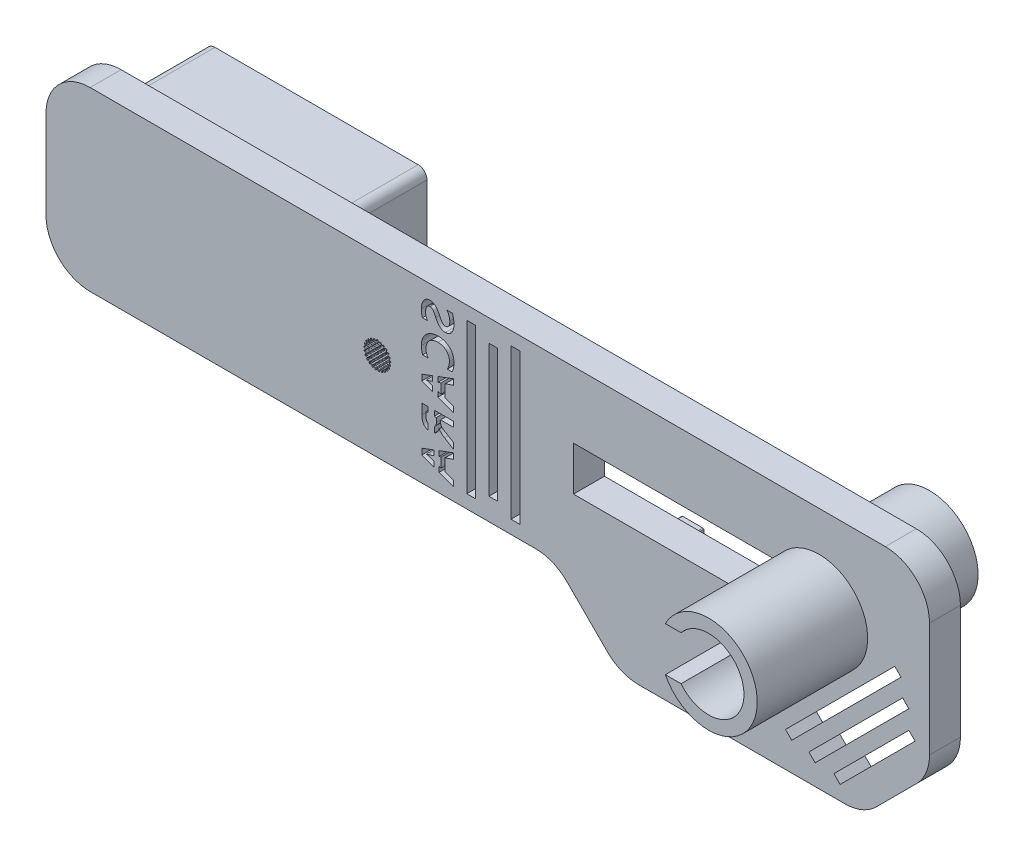
SolidWorks part; units mm, degrees
ref_plane "Alzado" through (0, 0, 0) normal (0, 0, 1) x (1, 0, 0)
ref_plane "Planta" through (0, 0, 0) normal (0, 1, 0) x (1, 0, 0)
ref_plane "Vista lateral" through (0, 0, 0) normal (1, 0, 0) x (0, 0, -1)
sketch "Croquis1" plane through (0, 0, 0) normal (0, 0, 1) x (1, 0, 0)
  line L0 (-64.25, 0) -> (10.75, 0) construction
  line L1 (0, 0) -> (0, -15.2525) construction
  line L2 (135.75, 20) -> (-64.25, 20)
  line L3 (135.75, 20) -> (135.75, -20)
  line L4 (135.75, -20) -> (-64.25, -20)
  line L5 (-64.25, 20) -> (-64.25, -20)
  line L56 (12.6265, 2.2468) -> (12.5286, 2.1823)
  line L57 (12.2759, 2.3659) -> (12.3069, 2.4789)
  line L58 (12.0088, 2.6428) -> (11.93, 2.5561)
  line L59 (11.6396, 2.6711) -> (11.6416, 2.7882)
  line L60 (11.312, 2.8728) -> (11.2572, 2.7692)
  line L61 (10.9474, 2.8084) -> (10.9201, 2.9223)
  line L62 (10.5799, 2.9223) -> (10.5526, 2.8084)
  line L63 (10.2428, 2.7692) -> (10.188, 2.8728)
  line L64 (9.8584, 2.7882) -> (9.8604, 2.6711)
  line L65 (9.57, 2.5561) -> (9.4912, 2.6428)
  line L66 (9.1931, 2.4789) -> (9.2241, 2.3659)
  line L67 (8.9714, 2.1823) -> (8.8735, 2.2468)
  line L68 (8.6255, 2.0138) -> (8.6836, 1.9121)
  line L69 (8.4846, 1.6715) -> (8.3738, 1.7095)
  line L70 (8.1914, 1.4222) -> (8.273, 1.3381)
  line L71 (8.1401, 1.0556) -> (8.0233, 1.0649)
  line L72 (7.9181, 0.7412) -> (8.0181, 0.6801)
  line L73 (7.9596, 0.3733) -> (7.8441, 0.3533)
  line L74 (7.8227, 0.0137) -> (7.9348, -0.0207)
  line L75 (7.9544, -0.3323) -> (7.8475, -0.3805)
  line L76 (7.9113, -0.7147) -> (8.0284, -0.7201)
  line L77 (8.1249, -1.0171) -> (8.0333, -1.0903)
  line L78 (8.1782, -1.3982) -> (8.293, -1.3744)
  line L79 (8.4603, -1.638) -> (8.3898, -1.7317)
  line L80 (8.6068, -1.9939) -> (8.7119, -1.9422)
  line L81 (8.9396, -2.156) -> (8.8946, -2.2642)
  line L82 (9.1699, -2.4642) -> (9.259, -2.3881)
  line L83 (9.5326, -2.5385) -> (9.516, -2.6545)
  line L84 (9.8324, -2.7798) -> (9.8997, -2.6838)
  line L85 (10.2022, -2.7615) -> (10.2149, -2.878)
  line L86 (10.5525, -2.9206) -> (10.5939, -2.811)
  line L87 (10.9061, -2.811) -> (10.9475, -2.9206)
  line L88 (11.2851, -2.878) -> (11.2978, -2.7615)
  line L89 (11.6003, -2.6838) -> (11.6676, -2.7798)
  line L90 (11.984, -2.6545) -> (11.9674, -2.5385)
  line L91 (12.241, -2.3881) -> (12.3301, -2.4642)
  line L92 (12.6054, -2.2642) -> (12.5604, -2.156)
  line L93 (12.7881, -1.9422) -> (12.8932, -1.9939)
  line L94 (13.1102, -1.7317) -> (13.0397, -1.638)
  line L95 (13.207, -1.3744) -> (13.3218, -1.3982)
  line L96 (13.4667, -1.0903) -> (13.3751, -1.0171)
  line L97 (13.4716, -0.7201) -> (13.5887, -0.7147)
  line L98 (13.6525, -0.3805) -> (13.5456, -0.3323)
  line L99 (13.5652, -0.0207) -> (13.6773, 0.0137)
  line L100 (13.6559, 0.3533) -> (13.5404, 0.3733)
  line L101 (13.4819, 0.6801) -> (13.5819, 0.7412)
  line L102 (13.4767, 1.0649) -> (13.3599, 1.0556)
  line L103 (13.227, 1.3381) -> (13.3086, 1.4222)
  line L104 (13.1262, 1.7095) -> (13.0154, 1.6715)
  line L105 (12.8164, 1.9121) -> (12.8745, 2.0138)
  line L106 (12.6265, 2.2468) -> (12.5286, 2.1823)
  line L107 (12.2759, 2.3659) -> (12.3069, 2.4789)
  line L108 (12.0088, 2.6428) -> (11.93, 2.5561)
  line L109 (11.6396, 2.6711) -> (11.6416, 2.7882)
  line L110 (11.312, 2.8728) -> (11.2572, 2.7692)
  line L111 (10.9474, 2.8084) -> (10.9201, 2.9223)
  line L112 (10.5799, 2.9223) -> (10.5526, 2.8084)
  line L113 (10.2428, 2.7692) -> (10.188, 2.8728)
  line L114 (9.8584, 2.7882) -> (9.8604, 2.6711)
  line L115 (9.57, 2.5561) -> (9.4912, 2.6428)
  line L116 (9.1931, 2.4789) -> (9.2241, 2.3659)
  line L117 (8.9714, 2.1823) -> (8.8735, 2.2468)
  line L118 (8.6255, 2.0138) -> (8.6836, 1.9121)
  line L119 (8.4846, 1.6715) -> (8.3738, 1.7095)
  line L120 (8.1914, 1.4222) -> (8.273, 1.3381)
  line L121 (8.1401, 1.0556) -> (8.0233, 1.0649)
  line L122 (7.9181, 0.7412) -> (8.0181, 0.6801)
  line L123 (7.9596, 0.3733) -> (7.8441, 0.3533)
  line L124 (7.8227, 0.0137) -> (7.9348, -0.0207)
  line L125 (7.9544, -0.3323) -> (7.8475, -0.3805)
  line L126 (7.9113, -0.7147) -> (8.0284, -0.7201)
  line L127 (8.1249, -1.0171) -> (8.0333, -1.0903)
  line L128 (8.1782, -1.3982) -> (8.293, -1.3744)
  line L129 (8.4603, -1.638) -> (8.3898, -1.7317)
  line L130 (8.6068, -1.9939) -> (8.7119, -1.9422)
  line L131 (8.9396, -2.156) -> (8.8946, -2.2642)
  line L132 (9.1699, -2.4642) -> (9.259, -2.3881)
  line L133 (9.5326, -2.5385) -> (9.516, -2.6545)
  line L134 (9.8324, -2.7798) -> (9.8997, -2.6838)
  line L135 (10.2022, -2.7615) -> (10.2149, -2.878)
  line L136 (10.5525, -2.9206) -> (10.5939, -2.811)
  line L137 (10.9061, -2.811) -> (10.9475, -2.9206)
  line L138 (11.2851, -2.878) -> (11.2978, -2.7615)
  line L139 (11.6003, -2.6838) -> (11.6676, -2.7798)
  line L140 (11.984, -2.6545) -> (11.9674, -2.5385)
  line L141 (12.241, -2.3881) -> (12.3301, -2.4642)
  line L142 (12.6054, -2.2642) -> (12.5604, -2.156)
  line L143 (12.7881, -1.9422) -> (12.8932, -1.9939)
  line L144 (13.1102, -1.7317) -> (13.0397, -1.638)
  line L145 (13.207, -1.3744) -> (13.3218, -1.3982)
  line L146 (13.4667, -1.0903) -> (13.3751, -1.0171)
  line L147 (13.4716, -0.7201) -> (13.5887, -0.7147)
  line L148 (13.6525, -0.3805) -> (13.5456, -0.3323)
  line L149 (13.5652, -0.0207) -> (13.6773, 0.0137)
  line L150 (13.6559, 0.3533) -> (13.5404, 0.3733)
  line L151 (13.4819, 0.6801) -> (13.5819, 0.7412)
  line L152 (13.4767, 1.0649) -> (13.3599, 1.0556)
  line L153 (13.227, 1.3381) -> (13.3086, 1.4222)
  line L154 (13.1262, 1.7095) -> (13.0154, 1.6715)
  line L155 (12.8164, 1.9121) -> (12.8745, 2.0138)
  arc A53 (12.8931, 2.1702) -> (12.7813, 2.2751) centre (10.75, 0) ccw
  arc A54 (12.2759, 2.3659) -> (12.5286, 2.1823) centre (12.4487, 2.3381) ccw
  arc A55 (12.2861, 2.635) -> (12.1517, 2.7088) centre (10.75, 0) ccw
  arc A56 (11.6396, 2.6711) -> (11.93, 2.5561) centre (11.8139, 2.6871) ccw
  arc A57 (11.5825, 2.9342) -> (11.434, 2.9723) centre (10.75, 0) ccw
  arc A58 (10.9474, 2.8084) -> (11.2572, 2.7692) centre (11.1122, 2.8672) ccw
  arc A59 (10.8267, 3.049) -> (10.6733, 3.049) centre (10.75, 0) ccw
  arc A60 (10.2428, 2.7692) -> (10.5526, 2.8084) centre (10.3878, 2.8672) ccw
  arc A61 (10.066, 2.9723) -> (9.9175, 2.9342) centre (10.75, 0) ccw
  arc A62 (9.57, 2.5561) -> (9.8604, 2.6711) centre (9.6861, 2.6871) ccw
  arc A63 (9.3483, 2.7088) -> (9.2139, 2.635) centre (10.75, 0) ccw
  arc A64 (8.9714, 2.1823) -> (9.2241, 2.3659) centre (9.0513, 2.3381) ccw
  arc A65 (8.7187, 2.2751) -> (8.6069, 2.1702) centre (10.75, 0) ccw
  arc A66 (8.4846, 1.6715) -> (8.6836, 1.9121) centre (8.5232, 1.8422) ccw
  arc A67 (8.2167, 1.6985) -> (8.1345, 1.569) centre (10.75, 0) ccw
  arc A68 (8.1401, 1.0556) -> (8.273, 1.3381) centre (8.135, 1.2305) ccw
  arc A69 (7.8739, 1.0151) -> (7.8265, 0.8693) centre (10.75, 0) ccw
  arc A70 (7.9596, 0.3733) -> (8.0181, 0.6801) centre (7.9112, 0.5415) ccw
  arc A71 (7.7118, 0.268) -> (7.7022, 0.1149) centre (10.75, 0) ccw
  arc A72 (7.9544, -0.3323) -> (7.9348, -0.0207) centre (7.8657, -0.1815) ccw
  arc A73 (7.7406, -0.496) -> (7.7693, -0.6466) centre (10.75, 0) ccw
  arc A74 (8.1249, -1.0171) -> (8.0284, -0.7201) centre (8.0014, -0.8931) ccw
  arc A75 (7.9585, -1.2289) -> (8.0238, -1.3676) centre (10.75, 0) ccw
  arc A76 (8.4603, -1.638) -> (8.293, -1.3744) centre (8.3099, -1.5485) ccw
  arc A77 (8.3518, -1.8845) -> (8.4495, -2.0026) centre (10.75, 0) ccw
  arc A78 (8.9396, -2.156) -> (8.7119, -1.9422) centre (8.7717, -2.1067) ccw
  arc A79 (8.8958, -2.4217) -> (9.0198, -2.5118) centre (10.75, 0) ccw
  arc A80 (9.5326, -2.5385) -> (9.259, -2.3881) centre (9.3577, -2.5325) ccw
  arc A81 (9.5563, -2.8067) -> (9.6988, -2.8631) centre (10.75, 0) ccw
  arc A82 (10.2022, -2.7615) -> (9.8997, -2.6838) centre (10.0313, -2.7992) ccw
  arc A83 (10.2918, -3.0154) -> (10.4439, -3.0346) centre (10.75, 0) ccw
  arc A84 (10.9061, -2.811) -> (10.5939, -2.811) centre (10.75, -2.89) ccw
  arc A85 (11.0561, -3.0346) -> (11.2082, -3.0154) centre (10.75, 0) ccw
  arc A86 (11.6003, -2.6838) -> (11.2978, -2.7615) centre (11.4687, -2.7992) ccw
  arc A87 (11.8012, -2.8631) -> (11.9437, -2.8067) centre (10.75, 0) ccw
  arc A88 (12.241, -2.3881) -> (11.9674, -2.5385) centre (12.1423, -2.5325) ccw
  arc A89 (12.4802, -2.5118) -> (12.6042, -2.4217) centre (10.75, 0) ccw
  arc A90 (12.7881, -1.9422) -> (12.5604, -2.156) centre (12.7283, -2.1067) ccw
  arc A91 (13.0505, -2.0026) -> (13.1482, -1.8845) centre (10.75, 0) ccw
  arc A92 (13.207, -1.3744) -> (13.0397, -1.638) centre (13.1901, -1.5485) ccw
  arc A93 (13.4762, -1.3676) -> (13.5415, -1.2289) centre (10.75, 0) ccw
  arc A94 (13.4716, -0.7201) -> (13.3751, -1.0171) centre (13.4986, -0.8931) ccw
  arc A95 (13.7307, -0.6466) -> (13.7594, -0.496) centre (10.75, 0) ccw
  arc A96 (13.5652, -0.0207) -> (13.5456, -0.3323) centre (13.6343, -0.1815) ccw
  arc A97 (13.7978, 0.1149) -> (13.7882, 0.268) centre (10.75, 0) ccw
  arc A98 (13.4819, 0.6801) -> (13.5404, 0.3733) centre (13.5888, 0.5415) ccw
  arc A99 (13.6735, 0.8693) -> (13.6261, 1.0151) centre (10.75, 0) ccw
  arc A100 (13.227, 1.3381) -> (13.3599, 1.0556) centre (13.365, 1.2305) ccw
  arc A101 (13.3655, 1.569) -> (13.2833, 1.6985) centre (10.75, 0) ccw
  arc A102 (12.8164, 1.9121) -> (13.0154, 1.6715) centre (12.9768, 1.8422) ccw
  arc A103 (12.8931, 2.1702) -> (12.7813, 2.2751) centre (10.75, 0) ccw
  arc A104 (12.2759, 2.3659) -> (12.5286, 2.1823) centre (12.4487, 2.3381) ccw
  arc A105 (12.2861, 2.635) -> (12.1517, 2.7088) centre (10.75, 0) ccw
  arc A106 (11.6396, 2.6711) -> (11.93, 2.5561) centre (11.8139, 2.6871) ccw
  arc A107 (11.5825, 2.9342) -> (11.434, 2.9723) centre (10.75, 0) ccw
  arc A108 (10.9474, 2.8084) -> (11.2572, 2.7692) centre (11.1122, 2.8672) ccw
  arc A109 (10.8267, 3.049) -> (10.6733, 3.049) centre (10.75, 0) ccw
  arc A110 (10.2428, 2.7692) -> (10.5526, 2.8084) centre (10.3878, 2.8672) ccw
  arc A111 (10.066, 2.9723) -> (9.9175, 2.9342) centre (10.75, 0) ccw
  arc A112 (9.57, 2.5561) -> (9.8604, 2.6711) centre (9.6861, 2.6871) ccw
  arc A113 (9.3483, 2.7088) -> (9.2139, 2.635) centre (10.75, 0) ccw
  arc A114 (8.9714, 2.1823) -> (9.2241, 2.3659) centre (9.0513, 2.3381) ccw
  arc A115 (8.7187, 2.2751) -> (8.6069, 2.1702) centre (10.75, 0) ccw
  arc A116 (8.4846, 1.6715) -> (8.6836, 1.9121) centre (8.5232, 1.8422) ccw
  arc A117 (8.2167, 1.6985) -> (8.1345, 1.569) centre (10.75, 0) ccw
  arc A118 (8.1401, 1.0556) -> (8.273, 1.3381) centre (8.135, 1.2305) ccw
  arc A119 (7.8739, 1.0151) -> (7.8265, 0.8693) centre (10.75, 0) ccw
  arc A120 (7.9596, 0.3733) -> (8.0181, 0.6801) centre (7.9112, 0.5415) ccw
  arc A121 (7.7118, 0.268) -> (7.7022, 0.1149) centre (10.75, 0) ccw
  arc A122 (7.9544, -0.3323) -> (7.9348, -0.0207) centre (7.8657, -0.1815) ccw
  arc A123 (7.7406, -0.496) -> (7.7693, -0.6466) centre (10.75, 0) ccw
  arc A124 (8.1249, -1.0171) -> (8.0284, -0.7201) centre (8.0014, -0.8931) ccw
  arc A125 (7.9585, -1.2289) -> (8.0238, -1.3676) centre (10.75, 0) ccw
  arc A126 (8.4603, -1.638) -> (8.293, -1.3744) centre (8.3099, -1.5485) ccw
  arc A127 (8.3518, -1.8845) -> (8.4495, -2.0026) centre (10.75, 0) ccw
  arc A128 (8.9396, -2.156) -> (8.7119, -1.9422) centre (8.7717, -2.1067) ccw
  arc A129 (8.8958, -2.4217) -> (9.0198, -2.5118) centre (10.75, 0) ccw
  arc A130 (9.5326, -2.5385) -> (9.259, -2.3881) centre (9.3577, -2.5325) ccw
  arc A131 (9.5563, -2.8067) -> (9.6988, -2.8631) centre (10.75, 0) ccw
  arc A132 (10.2022, -2.7615) -> (9.8997, -2.6838) centre (10.0313, -2.7992) ccw
  arc A133 (10.2918, -3.0154) -> (10.4439, -3.0346) centre (10.75, 0) ccw
  arc A134 (10.9061, -2.811) -> (10.5939, -2.811) centre (10.75, -2.89) ccw
  arc A135 (11.0561, -3.0346) -> (11.2082, -3.0154) centre (10.75, 0) ccw
  arc A136 (11.6003, -2.6838) -> (11.2978, -2.7615) centre (11.4687, -2.7992) ccw
  arc A137 (11.8012, -2.8631) -> (11.9437, -2.8067) centre (10.75, 0) ccw
  arc A138 (12.241, -2.3881) -> (11.9674, -2.5385) centre (12.1423, -2.5325) ccw
  arc A139 (12.4802, -2.5118) -> (12.6042, -2.4217) centre (10.75, 0) ccw
  arc A140 (12.7881, -1.9422) -> (12.5604, -2.156) centre (12.7283, -2.1067) ccw
  arc A141 (13.0505, -2.0026) -> (13.1482, -1.8845) centre (10.75, 0) ccw
  arc A142 (13.207, -1.3744) -> (13.0397, -1.638) centre (13.1901, -1.5485) ccw
  arc A143 (13.4762, -1.3676) -> (13.5415, -1.2289) centre (10.75, 0) ccw
  arc A144 (13.4716, -0.7201) -> (13.3751, -1.0171) centre (13.4986, -0.8931) ccw
  arc A145 (13.7307, -0.6466) -> (13.7594, -0.496) centre (10.75, 0) ccw
  arc A146 (13.5652, -0.0207) -> (13.5456, -0.3323) centre (13.6343, -0.1815) ccw
  arc A147 (13.7978, 0.1149) -> (13.7882, 0.268) centre (10.75, 0) ccw
  arc A148 (13.4819, 0.6801) -> (13.5404, 0.3733) centre (13.5888, 0.5415) ccw
  arc A149 (13.6735, 0.8693) -> (13.6261, 1.0151) centre (10.75, 0) ccw
  arc A150 (13.227, 1.3381) -> (13.3599, 1.0556) centre (13.365, 1.2305) ccw
  arc A151 (13.3655, 1.569) -> (13.2833, 1.6985) centre (10.75, 0) ccw
  arc A152 (12.8164, 1.9121) -> (13.0154, 1.6715) centre (12.9768, 1.8422) ccw
  spline S50 degree 3 poles (4995.73, -409.2684) (-67.7848, 26.1915) (12.1151, -1.3356) (12.9076, 2.1011) (12.9095, 2.115) (12.8385, 3.3562) (-8.2992, 15.6916) (-3096.0511, -3912.7164) knots -64.209924 -64.209924 -64.209924 -64.209924 0.5 0.5 0.75 0.75 22.340725 22.340725 22.340725 22.340725 only from (12.8745, 2.0138) to (12.8931, 2.1702)
  spline S51 degree 3 poles (-3620.5843, -3431.6551) (26.5308, -18.348) (13.985, 2.2945) (12.7252, 2.2881) (12.7115, 2.2853) (9.3593, 1.2884) (40.0278, -76.1834) (-376.9025, 4986.8401) knots -21.531354 -21.531354 -21.531354 -21.531354 0.25 0.25 0.5 0.5 64.672739 64.672739 64.672739 64.672739 only from (12.7813, 2.2751) to (12.6265, 2.2468)
  spline S52 degree 3 poles (4940.8986, 843.3036) (-71.831, 5.8378) (12.4044, -0.9542) (12.3173, 2.5717) (12.3157, 2.5856) (11.9382, 3.7702) (-11.603, 10.4612) (-2025.3923, -4562.4212) knots -64.209924 -64.209924 -64.209924 -64.209924 0.5 0.5 0.75 0.75 22.340725 22.340725 22.340725 22.340725 only from (12.3069, 2.4789) to (12.2861, 2.635)
  spline S53 degree 3 poles (-2653.0813, -4226.9195) (30.598, -13.847) (13.3128, 3.027) (12.0941, 2.7074) (12.0816, 2.7013) (9.0826, 0.9021) (58.054, -66.5088) (-1604.9003, 4733.7641) knots -21.531354 -21.531354 -21.531354 -21.531354 0.25 0.25 0.5 0.5 64.672739 64.672739 64.672739 64.672739 only from (12.1517, 2.7088) to (12.0088, 2.6428)
  spline S54 degree 3 poles (4576.2878, 2042.8878) (-70.6884, -14.8827) (12.5897, -0.5128) (11.6285, 2.8806) (11.6235, 2.8938) (10.9633, 3.9472) (-13.5024, 4.5736) (-826.7951, -4925.4523) knots -64.209924 -64.209924 -64.209924 -64.209924 0.5 0.5 0.75 0.75 22.340725 22.340725 22.340725 22.340725 only from (11.6416, 2.7882) to (11.5825, 2.9342)
  spline S55 degree 3 poles (-1518.2, -4756.5909) (33.418, -8.476) (12.4795, 3.5692) (11.3786, 2.9566) (11.368, 2.9476) (8.9107, 0.4591) (73.1079, -52.6553) (-2731.381, 4183.2483) knots -21.531354 -21.531354 -21.531354 -21.531354 0.25 0.25 0.5 0.5 64.672739 64.672739 64.672739 64.672739 only from (11.434, 2.9723) to (11.312, 2.8728)
  spline S56 degree 3 poles (3924.8075, 3114.1098) (-64.4287, -34.668) (12.6594, -0.0391) (10.8845, 3.0086) (10.8764, 3.0201) (9.9749, 3.8762) (-13.8779, -1.6014) (424.4281, -4978.9992) knots -64.209924 -64.209924 -64.209924 -64.209924 0.5 0.5 0.75 0.75 22.340725 22.340725 22.340725 22.340725 only from (10.9201, 2.9223) to (10.8267, 3.049)
  spline S57 degree 3 poles (-287.2492, -4987.3883) (34.8138, -2.5724) (11.5375, 3.8872) (10.6236, 3.0201) (10.6155, 3.0087) (8.8543, -0.0128) (84.2437, -35.4933) (-3685.5634, 3369.8836) knots -21.531354 -21.531354 -21.531354 -21.531354 0.25 0.25 0.5 0.5 64.672739 64.672739 64.672739 64.672739 only from (10.6733, 3.049) to (10.5799, 2.9223)
  spline S58 degree 3 poles (3027.3926, 3989.6608) (-53.4452, -52.275) (12.6092, 0.437) (10.1321, 2.9476) (10.1214, 2.9566) (9.0353, 3.5617) (-12.7059, -7.6758) (1649.6584, -4719.6972) knots -64.209924 -64.209924 -64.209924 -64.209924 0.5 0.5 0.75 0.75 22.340725 22.340725 22.340725 22.340725 only from (10.188, 2.8728) to (10.066, 2.9723)
  spline S59 degree 3 poles (962.4261, -4904.8097) (34.6975, 3.4928) (10.5461, 3.9609) (9.8765, 2.8938) (9.8715, 2.8807) (8.917, -0.4838) (90.7616, -16.101) (-4407.4929, 2344.7767) knots -21.531354 -21.531354 -21.531354 -21.531354 0.25 0.25 0.5 0.5 64.672739 64.672739 64.672739 64.672739 only from (9.9175, 2.9342) to (9.8584, 2.7882)
  spline S60 degree 3 poles (1940.4309, 4614.5268) (-38.4281, -66.5974) (12.4421, 0.8856) (9.4185, 2.7013) (9.4058, 2.7074) (8.2034, 3.0234) (-10.0601, -13.2679) (2771.91, -4163.8393) knots -64.209924 -64.209924 -64.209924 -64.209924 0.5 0.5 0.75 0.75 22.340725 22.340725 22.340725 22.340725 only from (9.4912, 2.6428) to (9.3483, 2.7088)
  spline S61 degree 3 poles (2152.304, -4514.0439) (33.0765, 9.3386) (9.5675, 3.7857) (9.1843, 2.5856) (9.1827, 2.5717) (9.0949, -0.9245) (92.252, 4.3029) (-4851.8079, 1172.3389) knots -21.531354 -21.531354 -21.531354 -21.531354 0.25 0.25 0.5 0.5 64.672739 64.672739 64.672739 64.672739 only from (9.2139, 2.635) to (9.1931, 2.4789)
  spline S62 degree 3 poles (732.2203, 4949.4451) (-20.321, -76.7352) (12.1687, 1.2786) (8.7885, 2.2853) (8.7748, 2.2881) (7.5315, 2.2951) (-6.1067, -18.0263) (3720.6678, -3346.3521) knots -64.209924 -64.209924 -64.209924 -64.209924 0.5 0.5 0.75 0.75 22.340725 22.340725 22.340725 22.340725 only from (8.8735, 2.2468) to (8.7187, 2.2751)
  spline S63 degree 3 poles (3207.6202, -3839.6441) (30.0527, 14.5976) (8.6631, 3.3727) (8.5904, 2.115) (8.5924, 2.1012) (9.3768, -1.307) (88.6214, 24.4364) (-4990.5906, -73.7612) knots -21.531354 -21.531354 -21.531354 -21.531354 0.25 0.25 0.5 0.5 64.672739 64.672739 64.672739 64.672739 only from (8.6069, 2.1702) to (8.6255, 2.0138)
  spline S64 degree 3 poles (-521.323, 4973.3715) (-0.2616, -82.0515) (11.8062, 1.5912) (8.2818, 1.7257) (8.2678, 1.725) (7.0619, 1.4226) (-1.0942, -21.6521) (4436.3179, -2318.6012) knots -64.209924 -64.209924 -64.209924 -64.209924 0.5 0.5 0.75 0.75 22.340725 22.340725 22.340725 22.340725 only from (8.3738, 1.7095) to (8.2167, 1.6985)
  spline S65 degree 3 poles (4062.0653, -2923.9853) (25.816, 18.9393) (7.8899, 2.7478) (8.1323, 1.5115) (8.1376, 1.4986) (9.745, -1.6075) (80.0978, 43.0345) (-4815.1206, -1315.2267) knots -21.531354 -21.531354 -21.531354 -21.531354 0.25 0.25 0.5 0.5 64.672739 64.672739 64.672739 64.672739 only from (8.1345, 1.569) to (8.1914, 1.4222)
  spline S66 degree 3 poles (-1741.4341, 4684.8028) (20.4897, -82.2122) (11.3773, 1.8039) (7.9302, 1.0577) (7.9168, 1.0535) (6.824, 0.4607) (4.6626, -23.9173) (4873.8932, -1145.1641) knots -64.209924 -64.209924 -64.209924 -64.209924 0.5 0.5 0.75 0.75 22.340725 22.340725 22.340725 22.340725 only from (8.0233, 1.0649) to (7.8739, 1.0151)
  spline S67 degree 3 poles (4661.9513, -1824.6018) (20.6326, 22.0911) (7.2964, 1.9502) (7.8387, 0.813) (7.847, 0.8018) (10.1764, -1.8069) (67.2169, 58.9286) (-4336.4234, -2474.0517) knots -21.531354 -21.531354 -21.531354 -21.531354 0.25 0.25 0.5 0.5 64.672739 64.672739 64.672739 64.672739 only from (7.8265, 0.8693) to (7.9181, 0.7412)
  spline S68 degree 3 poles (-2851.4491, 4101.8706) (40.6291, -77.2071) (10.9089, 1.9032) (7.7558, 0.3232) (7.7438, 0.3158) (6.8327, -0.5301) (10.8018, -24.6798) (5005.8993, 100.2278) knots -64.209924 -64.209924 -64.209924 -64.209924 0.5 0.5 0.75 0.75 22.340725 22.340725 22.340725 22.340725 only from (7.8441, 0.3533) to (7.7118, 0.268)
  spline S69 degree 3 poles (4969.5853, -610.5718) (14.8283, 23.8547) (6.9199, 1.03) (7.7279, 0.0635) (7.7388, 0.0547) (10.6437, -1.8928) (50.7879, 71.12) (-3584.5773, -3477.4228) knots -21.531354 -21.531354 -21.531354 -21.531354 0.25 0.25 0.5 0.5 64.672739 64.672739 64.672739 64.672739 only from (7.7022, 0.1149) to (7.8227, 0.0137)
  spline S70 degree 3 poles (-3781.6216, 3261.2028) (58.891, -67.3509) (10.4306, 1.8829) (7.7695, -0.4316) (7.7597, -0.4417) (7.0877, -1.4877) (16.9378, -23.8916) (4824.0419, 1339.3221) knots -64.209924 -64.209924 -64.209924 -64.209924 0.5 0.5 0.75 0.75 22.340725 22.340725 22.340725 22.340725 only from (7.8475, -0.3805) to (7.7406, -0.496)
  spline S71 degree 3 poles (4965.6374, 641.8226) (8.7677, 24.1195) (6.7841, 0.0452) (7.8071, -0.6901) (7.8198, -0.6959) (11.1178, -1.8597) (31.8432, 78.8427) (-2606.8236, -4262.2948) knots -21.531354 -21.531354 -21.531354 -21.531354 0.25 0.25 0.5 0.5 64.672739 64.672739 64.672739 64.672739 only from (7.7693, -0.6466) to (7.9113, -0.7147)
  spline S72 degree 3 poles (-4473.5054, 2215.6217) (74.1281, -53.2628) (9.9724, 1.7444) (7.9704, -1.1593) (7.9635, -1.1715) (7.5727, -2.3517) (22.685, -21.6021) (4339.7476, 2494.2619) knots -64.209924 -64.209924 -64.209924 -64.209924 0.5 0.5 0.75 0.75 22.340725 22.340725 22.340725 22.340725 only from (8.0333, -1.0903) to (7.9585, -1.2289)
  spline S73 degree 3 poles (4650.3557, 1853.8889) (2.8317, 22.8688) (6.8975, -0.9425) (8.0712, -1.4003) (8.0849, -1.4027) (11.5687, -1.7098) (11.5732, 81.6114) (-1464.5981, -4779.351) knots -21.531354 -21.531354 -21.531354 -21.531354 0.25 0.25 0.5 0.5 64.672739 64.672739 64.672739 64.672739 only from (8.0238, -1.3676) to (8.1782, -1.3982)
  spline S74 degree 3 poles (-4883.627, 1030.8249) (85.3828, -35.828) (9.563, 1.4962) (8.3461, -1.8141) (8.3424, -1.8277) (8.2573, -3.068) (27.6823, -17.9553) (3583.4465, 3492.478) knots -64.209924 -64.209924 -64.209924 -64.209924 0.5 0.5 0.75 0.75 22.340725 22.340725 22.340725 22.340725 only from (8.3898, -1.7317) to (8.3518, -1.8845)
  spline S75 degree 3 poles (4043.5505, 2949.4686) (-2.6067, 20.1812) (7.2529, -1.871) (8.5036, -2.0225) (8.5175, -2.0214) (11.9682, -1.4525) (-8.7486, 79.2521) (-229.6711, -4996.1031) knots -21.531354 -21.531354 -21.531354 -21.531354 0.25 0.25 0.5 0.5 64.672739 64.672739 64.672739 64.672739 only from (8.4495, -2.0026) to (8.6068, -1.9939)
  spline S76 degree 3 poles (-4986.2169, -218.7425) (91.9482, -16.1419) (9.2282, 1.154) (8.8727, -2.3549) (8.8726, -2.369) (9.0986, -3.5915) (31.6156, -13.1803) (2602.6597, 4271.2488) knots -64.209924 -64.209924 -64.209924 -64.209924 0.5 0.5 0.75 0.75 22.340725 22.340725 22.340725 22.340725 only from (8.8946, -2.2642) to (8.8958, -2.4217)
  spline S77 degree 3 poles (3183.3497, 3859.7224) (-7.206, 16.2254) (7.8281, -2.6819) (9.0771, -2.5176) (9.0903, -2.5131) (12.2912, -1.1039) (-27.8452, 71.9132) (1020.3625, -4898.9316) knots -21.531354 -21.531354 -21.531354 -21.531354 0.25 0.25 0.5 0.5 64.672739 64.672739 64.672739 64.672739 only from (9.0198, -2.5118) to (9.1699, -2.4642)
  spline S78 degree 3 poles (-4774.8289, -1454.5654) (93.4115, 4.5584) (8.9891, 0.7393) (9.5174, -2.7478) (9.5207, -2.7615) (10.0437, -3.8894) (34.2379, -7.5772) (1459.0137, 4781.6414) knots -64.209924 -64.209924 -64.209924 -64.209924 0.5 0.5 0.75 0.75 22.340725 22.340725 22.340725 22.340725 only from (9.516, -2.6545) to (9.5563, -2.8067)
  spline S79 degree 3 poles (2123.8027, 4527.4555) (-10.6769, 11.2502) (8.5868, -3.3243) (9.7558, -2.8545) (9.7675, -2.8469) (12.5173, -0.686) (-44.5168, 60.0556) (2206.9584, -4493.9422) knots -21.531354 -21.531354 -21.531354 -21.531354 0.25 0.25 0.5 0.5 64.672739 64.672739 64.672739 64.672739 only from (9.6988, -2.8631) to (9.8324, -2.7798)
  spline S80 degree 3 poles (-4262.7455, -2598.9926) (89.6809, 24.9722) (8.8605, 0.2781) (10.2394, -2.968) (10.2461, -2.9804) (11.0331, -3.9428) (35.3844, -1.4979) (224.368, 4991.5859) knots -64.209924 -64.209924 -64.209924 -64.209924 0.5 0.5 0.75 0.75 22.340725 22.340725 22.340725 22.340725 only from (10.2149, -2.878) to (10.2918, -3.0154)
  spline S81 degree 3 poles (931.4849, 4910.712) (-12.8016, 5.5681) (9.4815, -3.7578) (10.4969, -3.0121) (10.5063, -3.0018) (12.6324, -0.2249) (-57.7157, 44.4246) (3255.5585, -3806.5819) knots -21.531354 -21.531354 -21.531354 -21.531354 0.25 0.25 0.5 0.5 64.672739 64.672739 64.672739 64.672739 only from (10.4439, -3.0346) to (10.5525, -2.9206)
  spline S82 degree 3 poles (-3482.1426, -3580.1156) (80.9908, 43.817) (8.8507, -0.2005) (10.9936, -3.0018) (11.0031, -3.0121) (12.0048, -3.7485) (34.983, 4.6755) (-1023.7002, 4887.8907) knots -64.209924 -64.209924 -64.209924 -64.209924 0.5 0.5 0.75 0.75 22.340725 22.340725 22.340725 22.340725 only from (10.9475, -2.9206) to (11.0561, -3.0346)
  spline S83 degree 3 poles (-318.6861, 4985.4104) (-13.4464, -0.4639) (10.4559, -3.9552) (11.2539, -2.9804) (11.2605, -2.9681) (12.6292, 0.2503) (-66.6127, 26.0022) (4100.2753, -2880.0401) knots -21.531354 -21.531354 -21.531354 -21.531354 0.25 0.25 0.5 0.5 64.672739 64.672739 64.672739 64.672739 only from (11.2082, -3.0154) to (11.2851, -2.878)
  spline S84 degree 3 poles (-2482.0684, -4336.2867) (67.8872, 59.9086) (8.9603, -0.6665) (11.7325, -2.8469) (11.7442, -2.8545) (12.8976, -3.3187) (33.0589, 10.5551) (-2206.77, 4477.0713) knots -64.209924 -64.209924 -64.209924 -64.209924 0.5 0.5 0.75 0.75 22.340725 22.340725 22.340725 22.340725 only from (11.6676, -2.7798) to (11.8012, -2.8631)
  spline S85 degree 3 poles (-1548.1575, 4746.8572) (-12.5709, -6.4667) (11.4487, -3.9041) (11.9793, -2.7615) (11.9826, -2.7479) (12.5079, 0.7097) (-70.6487, 5.946) (4688.0322, -1772.5348) knots -21.531354 -21.531354 -21.531354 -21.531354 0.25 0.25 0.5 0.5 64.672739 64.672739 64.672739 64.672739 only from (11.9437, -2.8067) to (11.984, -2.6545)
  spline S86 degree 3 poles (-1325.3612, -4819.993) (51.1935, 72.2359) (9.1822, -1.0907) (12.4096, -2.5131) (12.4229, -2.5176) (13.6554, -2.6804) (29.7331, 15.7715) (-3250.5049, 3784.9411) knots -64.209924 -64.209924 -64.209924 -64.209924 0.5 0.5 0.75 0.75 22.340725 22.340725 22.340725 22.340725 only from (12.3301, -2.4642) to (12.4802, -2.5118)
  spline S87 degree 3 poles (-2679.6769, 4210.0414) (-10.23, -12.0632) (12.3977, -3.6077) (12.6274, -2.369) (12.6273, -2.355) (12.2761, 1.1246) (-69.5701, -14.4839) (4981.8982, -553.6546) knots -21.531354 -21.531354 -21.531354 -21.531354 0.25 0.25 0.5 0.5 64.672739 64.672739 64.672739 64.672739 only from (12.6042, -2.4217) to (12.6054, -2.2642)
  spline S88 degree 3 poles (-84.7013, -5000.8414) (31.9585, 80.0244) (9.5027, -1.4463) (12.9824, -2.0214) (12.9964, -2.0225) (14.2307, -1.8736) (25.2145, 19.9969) (-4089.3232, 2854.9891) knots -64.209924 -64.209924 -64.209924 -64.209924 0.5 0.5 0.75 0.75 22.340725 22.340725 22.340725 22.340725 only from (12.8932, -1.9939) to (13.0505, -2.0026)
  spline S89 degree 3 poles (-3642.1469, 3408.6932) (-6.5709, -16.9017) (13.2431, -3.0846) (13.1576, -1.8277) (13.154, -1.8142) (11.9485, 1.4688) (-63.4447, -34.0036) (4963.4088, 700.0138) knots -21.531354 -21.531354 -21.531354 -21.531354 0.25 0.25 0.5 0.5 64.672739 64.672739 64.672739 64.672739 only from (13.1482, -1.8845) to (13.1102, -1.7317)
  spline S90 degree 3 poles (1161.9561, -4867.4686) (11.391, 82.7846) (9.9016, -1.711) (13.415, -1.4027) (13.4288, -1.4003) (14.5873, -0.9491) (19.787, 22.9658) (-4670.5187, 1745.6476) knots -64.209924 -64.209924 -64.209924 -64.209924 0.5 0.5 0.75 0.75 22.340725 22.340725 22.340725 22.340725 only from (13.3218, -1.3982) to (13.4762, -1.3676)
  spline S91 degree 3 poles (-4375.092, 2393.1644) (-1.8234, -20.6783) (13.9319, -2.3677) (13.5365, -1.1715) (13.5296, -1.1593) (11.5456, 1.7207) (-52.6574, -51.3868) (4633.7255, 1909.6977) knots -21.531354 -21.531354 -21.531354 -21.531354 0.25 0.25 0.5 0.5 64.672739 64.672739 64.672739 64.672739 only from (13.5415, -1.2289) to (13.4667, -1.0903)
  spline S92 degree 3 poles (2336.2791, -4428.2548) (-9.2169, 80.3432) (10.3538, -1.8683) (13.6801, -0.6959) (13.6929, -0.6901) (14.7028, 0.035) (13.7918, 24.4917) (-4957.573, 526.6207) knots -64.209924 -64.209924 -64.209924 -64.209924 0.5 0.5 0.75 0.75 22.340725 22.340725 22.340725 22.340725 only from (13.5887, -0.7147) to (13.7307, -0.6466)
  spline S93 degree 3 poles (-4832.4585, 1227.2642) (3.7141, -23.1555) (14.4208, -1.502) (13.7403, -0.4417) (13.7306, -0.4317) (11.0927, 1.8645) (-37.8859, -65.5411) (4013.5637, 2999.3883) knots -21.531354 -21.531354 -21.531354 -21.531354 0.25 0.25 0.5 0.5 64.672739 64.672739 64.672739 64.672739 only from (13.7594, -0.496) to (13.6525, -0.3805)
  spline S94 degree 3 poles (3364.4805, -3710.7974) (-28.5701, 72.8535) (10.8308, -1.9081) (13.7611, 0.0546) (13.7721, 0.0635) (14.5699, 1.0169) (7.6054, 24.4787) (-4932.4492, -725.4957) knots -64.209924 -64.209924 -64.209924 -64.209924 0.5 0.5 0.75 0.75 22.340725 22.340725 22.340725 22.340725 only from (13.6773, 0.0137) to (13.7978, 0.1149)
  spline S95 degree 3 poles (-4985.5083, -15.7496) (9.6936, -24.1778) (14.679, -0.5419) (13.7562, 0.3158) (13.7443, 0.3231) (10.6182, 1.8912) (-20.0585, -75.5773) (3141.8904, 3900.6163) knots -21.531354 -21.531354 -21.531354 -21.531354 0.25 0.25 0.5 0.5 64.672739 64.672739 64.672739 64.672739 only from (13.7882, 0.268) to (13.6559, 0.3533)
  spline S96 degree 3 poles (4181.9547, -2760.1771) (-45.4527, 60.7862) (11.3028, -1.8281) (13.6529, 0.8018) (13.6613, 0.813) (14.197, 1.935) (1.6165, 22.9276) (-4596.7261, -1932.0266) knots -64.209924 -64.209924 -64.209924 -64.209924 0.5 0.5 0.75 0.75 22.340725 22.340725 22.340725 22.340725 only from (13.5819, 0.7412) to (13.6735, 0.8693)
  spline S97 degree 3 poles (-4824.6249, -1257.7737) (15.7396, -23.6809) (14.6903, 0.4522) (13.5832, 1.0535) (13.5699, 1.0577) (10.152, 1.799) (-0.2953, -80.8647) (2073.4761, 4556.7543) knots -21.531354 -21.531354 -21.531354 -21.531354 0.25 0.25 0.5 0.5 64.672739 64.672739 64.672739 64.672739 only from (13.6261, 1.0151) to (13.4767, 1.0649)
  spline S98 degree 3 poles (4737.3368, -1636.1246) (-58.8039, 44.8994) (11.7401, -1.6331) (13.3624, 1.4985) (13.3677, 1.5115) (13.6075, 2.7314) (-3.7984, 19.9359) (-3971.4983, -3017.1611) knots -64.209924 -64.209924 -64.209924 -64.209924 0.5 0.5 0.75 0.75 22.340725 22.340725 22.340725 22.340725 only from (13.3086, 1.4222) to (13.3655, 1.569)
  spline S99 degree 3 poles (-4359.9171, -2420.7673) (21.4721, -21.6961) (14.454, 1.4179) (13.2322, 1.725) (13.2183, 1.7257) (9.7234, 1.5937) (20.1619, -81.071) (875.453, 4926.5746) knots -21.531354 -21.531354 -21.531354 -21.531354 0.25 0.25 0.5 0.5 64.672739 64.672739 64.672739 64.672739 only from (13.2833, 1.6985) to (13.1262, 1.7095)
  spline S100 degree 3 poles (12.8745, 2.0138) (12.8876, 2.0368) (12.8985, 2.0614) (12.9076, 2.1011) (12.9095, 2.115) (12.9079, 2.1434) (12.9043, 2.1591) (12.8931, 2.1702) knots 0 0 0 0 0.5 0.5 0.75 0.75 1 1 1 1
  spline S101 degree 3 poles (12.7813, 2.2751) (12.7696, 2.2856) (12.7538, 2.2882) (12.7252, 2.2881) (12.7115, 2.2853) (12.6725, 2.2737) (12.6486, 2.2613) (12.6265, 2.2468) knots 0 0 0 0 0.25 0.25 0.5 0.5 1 1 1 1
  spline S102 degree 3 poles (12.3069, 2.4789) (12.314, 2.5044) (12.3183, 2.531) (12.3173, 2.5717) (12.3157, 2.5856) (12.3071, 2.6127) (12.2996, 2.627) (12.2861, 2.635) knots 0 0 0 0 0.5 0.5 0.75 0.75 1 1 1 1
  spline S103 degree 3 poles (12.1517, 2.7088) (12.1378, 2.716) (12.1218, 2.7147) (12.0941, 2.7074) (12.0816, 2.7013) (12.0467, 2.6804) (12.0266, 2.6624) (12.0088, 2.6428) knots 0 0 0 0 0.25 0.25 0.5 0.5 1 1 1 1
  spline S104 degree 3 poles (11.6416, 2.7882) (11.642, 2.8147) (11.6396, 2.8415) (11.6285, 2.8806) (11.6235, 2.8938) (11.6084, 2.9179) (11.5976, 2.9299) (11.5825, 2.9342) knots 0 0 0 0 0.5 0.5 0.75 0.75 1 1 1 1
  spline S105 degree 3 poles (11.434, 2.9723) (11.4187, 2.9758) (11.4036, 2.9705) (11.3786, 2.9566) (11.368, 2.9476) (11.3394, 2.9186) (11.3243, 2.8963) (11.312, 2.8728) knots 0 0 0 0 0.25 0.25 0.5 0.5 1 1 1 1
  spline S106 degree 3 poles (10.9201, 2.9223) (10.914, 2.9481) (10.905, 2.9734) (10.8845, 3.0086) (10.8764, 3.0201) (10.8558, 3.0397) (10.8424, 3.0486) (10.8267, 3.049) knots 0 0 0 0 0.5 0.5 0.75 0.75 1 1 1 1
  spline S107 degree 3 poles (10.6733, 3.049) (10.6576, 3.0486) (10.6443, 3.0398) (10.6236, 3.0201) (10.6155, 3.0087) (10.595, 2.9735) (10.586, 2.9481) (10.5799, 2.9223) knots 0 0 0 0 0.25 0.25 0.5 0.5 1 1 1 1
  spline S108 degree 3 poles (10.188, 2.8728) (10.1757, 2.8963) (10.1607, 2.9186) (10.1321, 2.9476) (10.1214, 2.9566) (10.0965, 2.9705) (10.0813, 2.9758) (10.066, 2.9723) knots 0 0 0 0 0.5 0.5 0.75 0.75 1 1 1 1
  spline S109 degree 3 poles (9.9175, 2.9342) (9.9024, 2.9299) (9.8917, 2.918) (9.8765, 2.8938) (9.8715, 2.8807) (9.8604, 2.8415) (9.858, 2.8147) (9.8584, 2.7882) knots 0 0 0 0 0.25 0.25 0.5 0.5 1 1 1 1
  spline S110 degree 3 poles (9.4912, 2.6428) (9.4734, 2.6624) (9.4534, 2.6803) (9.4185, 2.7013) (9.4058, 2.7074) (9.3783, 2.7147) (9.3623, 2.716) (9.3483, 2.7088) knots 0 0 0 0 0.5 0.5 0.75 0.75 1 1 1 1
  spline S111 degree 3 poles (9.2139, 2.635) (9.2004, 2.627) (9.193, 2.6129) (9.1843, 2.5856) (9.1827, 2.5717) (9.1817, 2.531) (9.186, 2.5044) (9.1931, 2.4789) knots 0 0 0 0 0.25 0.25 0.5 0.5 1 1 1 1
  spline S112 degree 3 poles (8.8735, 2.2468) (8.8514, 2.2613) (8.8276, 2.2737) (8.7885, 2.2853) (8.7748, 2.2881) (8.7463, 2.2882) (8.7304, 2.2856) (8.7187, 2.2751) knots 0 0 0 0 0.5 0.5 0.75 0.75 1 1 1 1
  spline S113 degree 3 poles (8.6069, 2.1702) (8.5957, 2.1591) (8.5921, 2.1435) (8.5904, 2.115) (8.5924, 2.1012) (8.6015, 2.0615) (8.6124, 2.0368) (8.6255, 2.0138) knots 0 0 0 0 0.25 0.25 0.5 0.5 1 1 1 1
  spline S114 degree 3 poles (8.3738, 1.7095) (8.3487, 1.7181) (8.3225, 1.7241) (8.2818, 1.7257) (8.2678, 1.725) (8.2402, 1.7181) (8.2254, 1.7115) (8.2167, 1.6985) knots 0 0 0 0 0.5 0.5 0.75 0.75 1 1 1 1
  spline S115 degree 3 poles (8.1345, 1.569) (8.1265, 1.5556) (8.1268, 1.5396) (8.1323, 1.5115) (8.1376, 1.4986) (8.1563, 1.4624) (8.173, 1.4412) (8.1914, 1.4222) knots 0 0 0 0 0.25 0.25 0.5 0.5 1 1 1 1
  spline S116 degree 3 poles (8.0233, 1.0649) (7.9969, 1.067) (7.97, 1.0663) (7.9302, 1.0577) (7.9168, 1.0535) (7.8918, 1.0399) (7.8791, 1.0299) (7.8739, 1.0151) knots 0 0 0 0 0.5 0.5 0.75 0.75 1 1 1 1
  spline S117 degree 3 poles (7.8265, 0.8693) (7.822, 0.8542) (7.8264, 0.8388) (7.8387, 0.813) (7.847, 0.8018) (7.8741, 0.7715) (7.8955, 0.7551) (7.9181, 0.7412) knots 0 0 0 0 0.25 0.25 0.5 0.5 1 1 1 1
  spline S118 degree 3 poles (7.8441, 0.3533) (7.818, 0.3488) (7.7922, 0.3414) (7.7558, 0.3232) (7.7438, 0.3158) (7.723, 0.2964) (7.7132, 0.2836) (7.7118, 0.268) knots 0 0 0 0 0.5 0.5 0.75 0.75 1 1 1 1
  spline S119 degree 3 poles (7.7022, 0.1149) (7.7016, 0.0992) (7.7096, 0.0854) (7.7279, 0.0635) (7.7388, 0.0547) (7.7726, 0.032) (7.7974, 0.0214) (7.8227, 0.0137) knots 0 0 0 0 0.25 0.25 0.5 0.5 1 1 1 1
  spline S120 degree 3 poles (7.8475, -0.3805) (7.8234, -0.3913) (7.8002, -0.4049) (7.7695, -0.4316) (7.7597, -0.4417) (7.7443, -0.4657) (7.738, -0.4805) (7.7406, -0.496) knots 0 0 0 0 0.5 0.5 0.75 0.75 1 1 1 1
  spline S121 degree 3 poles (7.7693, -0.6466) (7.7727, -0.662) (7.7839, -0.6734) (7.8071, -0.6901) (7.8198, -0.6959) (7.8582, -0.7094) (7.8849, -0.7135) (7.9113, -0.7147) knots 0 0 0 0 0.25 0.25 0.5 0.5 1 1 1 1
  spline S122 degree 3 poles (8.0333, -1.0903) (8.0127, -1.1069) (7.9935, -1.1257) (7.9704, -1.1593) (7.9635, -1.1715) (7.9546, -1.1985) (7.9522, -1.2145) (7.9585, -1.2289) knots 0 0 0 0 0.5 0.5 0.75 0.75 1 1 1 1
  spline S123 degree 3 poles (8.0238, -1.3676) (8.0308, -1.3816) (8.0445, -1.3899) (8.0712, -1.4003) (8.0849, -1.4027) (8.1255, -1.4063) (8.1523, -1.4036) (8.1782, -1.3982) knots 0 0 0 0 0.25 0.25 0.5 0.5 1 1 1 1
  spline S124 degree 3 poles (8.3898, -1.7317) (8.3739, -1.7528) (8.3601, -1.7759) (8.3461, -1.8141) (8.3424, -1.8277) (8.3405, -1.8561) (8.3421, -1.8721) (8.3518, -1.8845) knots 0 0 0 0 0.5 0.5 0.75 0.75 1 1 1 1
  spline S125 degree 3 poles (8.4495, -2.0026) (8.4599, -2.0144) (8.4752, -2.0191) (8.5036, -2.0225) (8.5175, -2.0214) (8.5577, -2.0148) (8.583, -2.0055) (8.6068, -1.9939) knots 0 0 0 0 0.25 0.25 0.5 0.5 1 1 1 1
  spline S126 degree 3 poles (8.8946, -2.2642) (8.8845, -2.2887) (8.8768, -2.3144) (8.8727, -2.3549) (8.8726, -2.369) (8.8777, -2.397) (8.8833, -2.4121) (8.8958, -2.4217) knots 0 0 0 0 0.5 0.5 0.75 0.75 1 1 1 1
  spline S127 degree 3 poles (9.0198, -2.5118) (9.0328, -2.5207) (9.0488, -2.5213) (9.0771, -2.5176) (9.0903, -2.5131) (9.1276, -2.4967) (9.1498, -2.4814) (9.1699, -2.4642) knots 0 0 0 0 0.25 0.25 0.5 0.5 1 1 1 1
  spline S128 degree 3 poles (9.516, -2.6545) (9.5123, -2.6807) (9.5113, -2.7076) (9.5174, -2.7478) (9.5207, -2.7615) (9.5327, -2.7873) (9.5418, -2.8005) (9.5563, -2.8067) knots 0 0 0 0 0.5 0.5 0.75 0.75 1 1 1 1
  spline S129 degree 3 poles (9.6988, -2.8631) (9.7136, -2.8686) (9.7293, -2.8652) (9.7558, -2.8545) (9.7675, -2.8469) (9.7995, -2.8218) (9.8172, -2.8014) (9.8324, -2.7798) knots 0 0 0 0 0.25 0.25 0.5 0.5 1 1 1 1
  spline S130 degree 3 poles (10.2149, -2.878) (10.2178, -2.9043) (10.2235, -2.9306) (10.2394, -2.968) (10.2461, -2.9804) (10.2641, -3.0025) (10.2763, -3.013) (10.2918, -3.0154) knots 0 0 0 0 0.5 0.5 0.75 0.75 1 1 1 1
  spline S131 degree 3 poles (10.4439, -3.0346) (10.4595, -3.0362) (10.4739, -3.029) (10.4969, -3.0121) (10.5063, -3.0018) (10.5311, -2.9695) (10.5432, -2.9454) (10.5525, -2.9206) knots 0 0 0 0 0.25 0.25 0.5 0.5 1 1 1 1
  spline S132 degree 3 poles (10.9475, -2.9206) (10.9568, -2.9454) (10.9689, -2.9694) (10.9936, -3.0018) (11.0031, -3.0121) (11.026, -3.029) (11.0404, -3.0362) (11.0561, -3.0346) knots 0 0 0 0 0.5 0.5 0.75 0.75 1 1 1 1
  spline S133 degree 3 poles (11.2082, -3.0154) (11.2237, -3.013) (11.2358, -3.0026) (11.2539, -2.9804) (11.2605, -2.9681) (11.2765, -2.9306) (11.2822, -2.9043) (11.2851, -2.878) knots 0 0 0 0 0.25 0.25 0.5 0.5 1 1 1 1
  spline S134 degree 3 poles (11.6676, -2.7798) (11.6828, -2.8014) (11.7004, -2.8217) (11.7325, -2.8469) (11.7442, -2.8545) (11.7706, -2.8652) (11.7864, -2.8686) (11.8012, -2.8631) knots 0 0 0 0 0.5 0.5 0.75 0.75 1 1 1 1
  spline S135 degree 3 poles (11.9437, -2.8067) (11.9582, -2.8006) (11.9673, -2.7874) (11.9793, -2.7615) (11.9826, -2.7479) (11.9887, -2.7076) (11.9877, -2.6807) (11.984, -2.6545) knots 0 0 0 0 0.25 0.25 0.5 0.5 1 1 1 1
  spline S136 degree 3 poles (12.3301, -2.4642) (12.3502, -2.4814) (12.3723, -2.4967) (12.4096, -2.5131) (12.4229, -2.5176) (12.4511, -2.5213) (12.4672, -2.5207) (12.4802, -2.5118) knots 0 0 0 0 0.5 0.5 0.75 0.75 1 1 1 1
  spline S137 degree 3 poles (12.6042, -2.4217) (12.6167, -2.4121) (12.6222, -2.3971) (12.6274, -2.369) (12.6273, -2.355) (12.6232, -2.3145) (12.6155, -2.2887) (12.6054, -2.2642) knots 0 0 0 0 0.25 0.25 0.5 0.5 1 1 1 1
  spline S138 degree 3 poles (12.8932, -1.9939) (12.917, -2.0055) (12.9422, -2.0148) (12.9824, -2.0214) (12.9964, -2.0225) (13.0247, -2.0191) (13.0401, -2.0145) (13.0505, -2.0026) knots 0 0 0 0 0.5 0.5 0.75 0.75 1 1 1 1
  spline S139 degree 3 poles (13.1482, -1.8845) (13.1579, -1.8721) (13.1595, -1.8562) (13.1576, -1.8277) (13.154, -1.8142) (13.1399, -1.776) (13.1261, -1.7528) (13.1102, -1.7317) knots 0 0 0 0 0.25 0.25 0.5 0.5 1 1 1 1
  spline S140 degree 3 poles (13.3218, -1.3982) (13.3477, -1.4036) (13.3744, -1.4063) (13.415, -1.4027) (13.4288, -1.4003) (13.4554, -1.3899) (13.4692, -1.3816) (13.4762, -1.3676) knots 0 0 0 0 0.5 0.5 0.75 0.75 1 1 1 1
  spline S141 degree 3 poles (13.5415, -1.2289) (13.5478, -1.2145) (13.5455, -1.1986) (13.5365, -1.1715) (13.5296, -1.1593) (13.5065, -1.1258) (13.4873, -1.1069) (13.4667, -1.0903) knots 0 0 0 0 0.25 0.25 0.5 0.5 1 1 1 1
  spline S142 degree 3 poles (13.5887, -0.7147) (13.6151, -0.7135) (13.6417, -0.7095) (13.6801, -0.6959) (13.6929, -0.6901) (13.716, -0.6735) (13.7273, -0.662) (13.7307, -0.6466) knots 0 0 0 0 0.5 0.5 0.75 0.75 1 1 1 1
  spline S143 degree 3 poles (13.7594, -0.496) (13.7619, -0.4805) (13.7557, -0.4658) (13.7403, -0.4417) (13.7306, -0.4317) (13.6999, -0.4049) (13.6766, -0.3913) (13.6525, -0.3805) knots 0 0 0 0 0.25 0.25 0.5 0.5 1 1 1 1
  spline S144 degree 3 poles (13.6773, 0.0137) (13.7026, 0.0214) (13.7273, 0.032) (13.7611, 0.0546) (13.7721, 0.0635) (13.7903, 0.0853) (13.7984, 0.0992) (13.7978, 0.1149) knots 0 0 0 0 0.5 0.5 0.75 0.75 1 1 1 1
  spline S145 degree 3 poles (13.7882, 0.268) (13.7868, 0.2836) (13.7771, 0.2963) (13.7562, 0.3158) (13.7443, 0.3231) (13.7079, 0.3414) (13.682, 0.3488) (13.6559, 0.3533) knots 0 0 0 0 0.25 0.25 0.5 0.5 1 1 1 1
  spline S146 degree 3 poles (13.5819, 0.7412) (13.6045, 0.755) (13.6258, 0.7714) (13.6529, 0.8018) (13.6613, 0.813) (13.6736, 0.8387) (13.678, 0.8542) (13.6735, 0.8693) knots 0 0 0 0 0.5 0.5 0.75 0.75 1 1 1 1
  spline S147 degree 3 poles (13.6261, 1.0151) (13.6209, 1.0299) (13.6083, 1.0399) (13.5832, 1.0535) (13.5699, 1.0577) (13.5301, 1.0663) (13.5031, 1.067) (13.4767, 1.0649) knots 0 0 0 0 0.25 0.25 0.5 0.5 1 1 1 1
  spline S148 degree 3 poles (13.3086, 1.4222) (13.327, 1.4412) (13.3436, 1.4623) (13.3624, 1.4985) (13.3677, 1.5115) (13.3732, 1.5394) (13.3736, 1.5555) (13.3655, 1.569) knots 0 0 0 0 0.5 0.5 0.75 0.75 1 1 1 1
  spline S149 degree 3 poles (13.2833, 1.6985) (13.2746, 1.7115) (13.2599, 1.718) (13.2322, 1.725) (13.2183, 1.7257) (13.1776, 1.7242) (13.1513, 1.7181) (13.1262, 1.7095) knots 0 0 0 0 0.25 0.25 0.5 0.5 1 1 1 1
  dimension "D3" = 75
  dimension "D4" = 10.75
  dimension "D1" = 200
  dimension "D2" = 40
  dimension "D5" = 0
extrude "Saliente-Extruir1" add sketch "Croquis1" along normal blind 7
sketch "Croquis2" plane through (0, 0, 7) normal (0, 0, 1) x (1, 0, 0)
  line L0 (10.75, 0) -> (110.75, 0) construction
  line L1 (10.75, 0) -> (10.75, -5.2306) construction
  line L7 (55.16, 5) -> (104.505, 5)
  line L8 (55.16, 5) -> (55.16, -5)
  line L9 (55.16, -5) -> (104.505, -5)
  arc A0 (104.505, -5) -> (104.505, 5) centre (110.75, 0) ccw
  dimension "D2" = 16
  dimension "D1" = 100
  dimension "D5" = 10
  dimension "D6" = 5
extrude "Cortar-Extruir1" cut sketch "Croquis2" against normal blind 10
sketch "Croquis5" plane through (0, 0, 7) normal (0, 0, 1) x (1, 0, 0)
  line L0 (104.505, 5) -> (100.952, 5)
  line L1 (104.505, 5) -> (55.16, 5) construction
  line L2 (104.505, -5) -> (100.952, -5)
  line L3 (55.16, -5) -> (104.505, -5) construction
  arc A0 (100.952, -5) -> (100.952, 5) centre (110.75, 0) ccw
  arc A2 (104.505, -5) -> (104.505, 5) centre (110.75, 0) ccw
  dimension "D1" = 22
extrude "Saliente-Extruir3" add sketch "Croquis5" along normal mid plane 50
sketch "Croquis8" plane through (0, 0, 0) normal (0, 0, -1) x (-1, 0, 0)
  line L0 (0, 0) -> (-135.75, 0) construction
  line L1 (-135.75, -20) -> (-135.75, 20) construction
  line L2 (-135.75, -20) -> (-120.75, -35)
  line L3 (-120.75, -35) -> (-65.75, -35)
  line L4 (-65.75, -35) -> (-50.75, -20)
  line L5 (64.25, -20) -> (-135.75, -20) construction
  line L6 (-135.75, -20) -> (-50.75, -20)
  dimension "D1" = 55
  dimension "D2" = 15
  dimension "D3" = 15
extrude "Saliente-Extruir5" add sketch "Croquis8" against normal blind 7
sketch "Croquis9" plane through (0, 0, 0) normal (0, 0, -1) x (-1, 0, 0)
  line L0 (-100.952, -5) -> (-55.16, -5) construction
  line L1 (-60.66, -16) -> (-65.66, -16)
  line L2 (-60.66, -16) -> (-60.66, -24)
  line L3 (-60.66, -24) -> (-65.66, -24)
  line L4 (-65.66, -16) -> (-65.66, -24)
  line L5 (-55.16, -5) -> (-55.16, 5) construction
  line L7 (-88.66, -24) -> (-93.66, -24)
  line L8 (-88.66, -24) -> (-88.66, -16)
  line L9 (-88.66, -16) -> (-93.66, -16)
  line L10 (-93.66, -24) -> (-93.66, -16)
  dimension "D1" = 11
  dimension "D2" = 5
  dimension "D3" = 5.5
  dimension "D4" = 8
  dimension "D5" = 11
  dimension "D6" = 5
  dimension "D7" = 8
  dimension "D8" = 33.5
extrude "Saliente-Extruir6" add sketch "Croquis9" along normal blind 12
sketch "Croquis10" plane through (0, -16, 0) normal (0, 1, 0) x (1, 0, 0)
  line L0 (135.75, 0) -> (-64.25, 0) construction
  circle A0 centre (63.26, 6.3) radius 1
  circle A1 centre (91.06, 6.3) radius 1
  dimension "D1" = 2
  dimension "D2" = 2
  dimension "D3" = 6.3
  dimension "D4" = 6.3
  dimension "D5" = 27.8
  dimension "D6" = 63.26
extrude "Cortar-Extruir2" cut sketch "Croquis10" against normal blind 4
sketch "Croquis11" plane through (0, 0, 0) normal (0, 0, -1) x (-1, 0, 0)
  line L0 (0, 0) -> (64.25, 0) construction
  line L1 (64.25, 20) -> (64.25, -20) construction
  line L2 (8, 9) -> (11, 9)
  line L3 (5, 15) -> (55, 15)
  line L4 (5, 15) -> (5, -15)
  line L5 (5, -15) -> (55, -15)
  line L6 (55, 15) -> (55, -15)
  line L7 (11, 12) -> (52, 12)
  line L8 (8, 9) -> (8, -12)
  line L9 (8, -12) -> (49, -12)
  line L10 (52, 12) -> (52, -9)
  line L11 (11, 9) -> (11, 12)
  line L12 (49, -12) -> (49, -9)
  line L13 (49, -9) -> (52, -9)
  point P16 (11, 10.5)
  dimension "D1" = 30
  dimension "D2" = 3
  dimension "D3" = 3
  dimension "D4" = 3
  dimension "D5" = 3
  dimension "D6" = 50
  dimension "D7" = 5
  dimension "D8" = 15
  dimension "D9" = 6
  dimension "D10" = 6
  dimension "D11" = 6
  dimension "D12" = 6
extrude "Saliente-Extruir7" add sketch "Croquis11" along normal blind 20
sketch "Croquis12" plane through (0, 0, -20) normal (0, 0, -1) x (-1, 0, 0)
  line L0 (55, 15) -> (5, 15) construction
  line L2 (5, 15) -> (5, -15) construction
  line L3 (49, -12) -> (49, -9) construction
  line L6 (5, -15) -> (55, -15) construction
  circle A0 centre (8, 12) radius 1.5
  circle A1 centre (52, -12) radius 1.5
  dimension "D1" = 3
  dimension "D2" = 3
  dimension "D3" = 3
  dimension "D4" = 3
  dimension "D5" = 3
  dimension "D6" = 3
extrude "Cortar-Extruir3" cut sketch "Croquis12" against normal blind 10
fillet "Redondeo1" radius 2 6 edges at (-49, -9, -10) (-11, 9, -10) (-5, 15, -10) (-55, 15, -10) (-55, -15, -10) (-5, -15, -10)
fillet "Redondeo2" radius 10 7 edges at (-64.25, 20, 3.5) (-64.25, -20, 3.5) (50.75, -20, 3.5) (65.75, -35, 3.5) (120.75, -35, 3.5) (135.75, -20, 3.5) (135.75, 20, 3.5)
fillet "Redondeo3" radius 0.2 8 edges at (88.66, -16, -6) (93.66, -16, -6) (93.66, -24, -6) (88.66, -24, -6) (60.66, -24, -6) (65.66, -24, -6) (65.66, -16, -6) (60.66, -16, -6)
sketch "Croquis13" plane through (0, 0, 0) normal (0, 0, -1) x (-1, 0, 0)
  line L0 (-28.01, 20) -> (-28.01, -20) construction
  line L1 (-125.75, 20) -> (54.25, 20) construction
  line L2 (54.25, -20) -> (-46.6079, -20) construction
  text T0 "SCARA" font "Yu Gothic UI" height in points 28
  dimension "D1" = 28.01
extrude "Cortar-Extruir6" cut sketch "Croquis13" against normal blind 7
sketch "Croquis15" plane through (0, 0, 0) normal (0, 0, -1) x (-1, 0, 0)
  line L0 (-23.8713, -1.4088) -> (-23.8713, 3.3266) construction
  line L2 (-24.4713, -1.5411) -> (-23.2713, -1.5411)
  line L3 (-24.4713, -1.5411) -> (-24.4713, 3.4589)
  line L4 (-24.4713, 3.4589) -> (-23.2713, 3.4589)
  line L5 (-23.2713, -1.5411) -> (-23.2713, 3.4589)
  line L6 (-24.4713, -1.5411) -> (-23.2713, 3.4589) construction
  line L7 (-24.4713, 3.4589) -> (-23.2713, -1.5411) construction
  line L8 (-25.1713, 1.8052) -> (-25.1713, -0.3844) construction
  line L10 (-25.1713, 0.7104) -> (-24.6397, 0.7104) construction
  line L11 (-22.9477, -4.308) -> (-22.9477, -8.9914) construction
  line L12 (-28.01, -4.308) -> (-20.8187, -4.308) construction
  line L13 (-24.1305, -6.4799) -> (-20.8187, -6.4799) construction
  line L14 (-23.6477, -9.6497) -> (-22.2477, -9.6497)
  line L15 (-23.6477, -9.6497) -> (-23.6477, -3.6497)
  line L16 (-23.6477, -3.6497) -> (-22.2477, -3.6497)
  line L17 (-22.2477, -9.6497) -> (-22.2477, -3.6497)
  line L18 (-23.6477, -9.6497) -> (-22.2477, -3.6497) construction
  line L19 (-23.6477, -3.6497) -> (-22.2477, -9.6497) construction
  line L20 (-20.8187, -4.308) -> (-20.8187, -6.6632) construction
  line L21 (-24.1305, -16.746) -> (-24.1305, -11.0619) construction
  line L22 (-25.1713, -13.8046) -> (-24.6397, -13.8046) construction
  line L23 (-25.1713, -12.7098) -> (-25.1713, -14.8995) construction
  line L25 (-24.7305, -16.4039) -> (-23.5305, -16.4039)
  line L26 (-24.7305, -16.4039) -> (-24.7305, -11.4039)
  line L27 (-24.7305, -11.4039) -> (-23.5305, -11.4039)
  line L28 (-23.5305, -16.4039) -> (-23.5305, -11.4039)
  line L29 (-24.7305, -16.4039) -> (-23.5305, -11.4039) construction
  line L30 (-24.7305, -11.4039) -> (-23.5305, -16.4039) construction
  spline S0 degree 3 poles (-22.7555, -8.9992) (-22.8177, -8.9977) (-22.9398, -8.9947) (-23.1195, -8.9739) (-23.2911, -8.9385) (-23.4548, -8.8894) (-23.6098, -8.8277) (-23.7559, -8.7528) (-23.8936, -8.6671) (-24.023, -8.5698) (-24.1405, -8.4588) (-24.2531, -8.3412) (-24.3529, -8.2095) (-24.4466, -8.0695) (-24.5296, -7.9188) (-24.5994, -7.7575) (-24.6648, -7.5897) (-24.6968, -7.4722) (-24.713, -7.4128) knots 0 0 0 0 0.068223 0.134123 0.198211 0.260345 0.321528 0.381051 0.440349 0.49943 0.558389 0.617717 0.677885 0.739557 0.802512 0.866453 0.932372 1 1 1 1 construction
  point P2 (-23.8713, 0.9589)
  point P17 (-22.9477, -6.6497)
  point P33 (-24.1305, -13.9039)
  dimension "D1" = 0.6
  dimension "D2" = 5
  dimension "D3" = 0.7
  dimension "D4" = 2.7485
  dimension "D5" = 6
  dimension "D6" = 0.7
  dimension "D7" = 2.8302
  dimension "D8" = 5
  dimension "D9" = 0.6
  dimension "D10" = 2.4007
extrude "Saliente-Extruir9" add sketch "Croquis15" against normal blind 7
sketch "Croquis16" plane through (0, 0, 0) normal (0, 0, -1) x (-1, 0, 0)
  line L1 (-125.75, 20) -> (54.25, 20) construction
  line L2 (54.25, -20) -> (-46.6079, -20) construction
  line L3 (-28.0155, 20) -> (-28.0155, -20) construction
  line L4 (-33.01, 17) -> (-31.01, 17)
  line L5 (-33.01, 17) -> (-33.01, -17)
  line L6 (-33.01, -17) -> (-31.01, -17)
  line L7 (-31.01, 17) -> (-31.01, -17)
  line L8 (-43.01, 17) -> (-41.01, 17)
  line L9 (-38.01, 15) -> (-36.01, 15)
  line L10 (-38.01, 15) -> (-38.01, -15)
  line L11 (-38.01, -15) -> (-36.01, -15)
  line L12 (-36.01, 15) -> (-36.01, -15)
  line L13 (-43.01, 17) -> (-43.01, -17)
  line L14 (-43.01, -17) -> (-41.01, -17)
  line L15 (-41.01, 17) -> (-41.01, -17)
  dimension "D1" = 2
  dimension "D2" = 3
  dimension "D3" = 3
  dimension "D4" = 3
  dimension "D5" = 3
  dimension "D6" = 5
  dimension "D7" = 5
  dimension "D8" = 2
  dimension "D9" = 3
  dimension "D10" = 2
  dimension "D11" = 3
extrude "Cortar-Extruir7" cut sketch "Croquis16" against normal blind 7
sketch "Croquis17" plane through (0, 0, 0) normal (0, 0, -1) x (-1, 0, 0)
  line L0 (-132.4926, -14.7721) -> (-115.5221, -31.7426)
  line L1 (-115.5221, -31.7426) -> (-114.1079, -30.3284)
  line L2 (-114.1079, -30.3284) -> (-131.0784, -13.3579)
  line L3 (-131.0784, -13.3579) -> (-132.4926, -14.7721)
  line L4 (-132.8211, -22.9289) -> (-123.6789, -32.0711) construction
  line L10 (-109.8652, -30.3284) -> (-131.0784, -9.1152)
  line L11 (-131.0784, -9.1152) -> (-129.6642, -7.701)
  line L12 (-129.6642, -7.701) -> (-108.451, -28.9142)
  line L13 (-108.451, -28.9142) -> (-109.8652, -30.3284)
  line L14 (-128.25, -27.5) -> (-109.6013, -8.8513) construction
  line L15 (-129.3107, -3.8119) -> (-104.5619, -28.5607)
  line L16 (-104.5619, -28.5607) -> (-103.1477, -27.1464)
  line L17 (-103.1477, -27.1464) -> (-127.8964, -2.3977)
  line L18 (-127.8964, -2.3977) -> (-129.3107, -3.8119)
  dimension "D1" = 2
  dimension "D2" = 6
  dimension "D3" = 24
  dimension "D4" = 2
  dimension "D5" = 30
  dimension "D6" = 3
  dimension "D7" = 15
  dimension "D8" = 12
  dimension "D9" = 2
  dimension "D10" = 35
  dimension "D11" = 17.5
  dimension "D12" = 3
extrude "Cortar-Extruir8" cut sketch "Croquis17" against normal blind 7
sketch "Croquis19" plane through (0, 0, 0) normal (0, 0, -1) x (-1, 0, 0)
  circle A0 centre (-10.75, 0) radius 3.5
  circle A1 centre (-10.75, 0) radius 1.1
  dimension "D1" = 7
  dimension "D2" = 2.2
extrude "Saliente-Extruir10" add sketch "Croquis19" against normal blind 3
sketch "Croquis20" plane through (0, 0, 0) normal (0, 0, -1) x (-1, 0, 0)
  circle A0 centre (-10.75, 0) radius 2.75
  dimension "D1" = 5.5
extrude "Cortar-Extruir9" cut sketch "Croquis20" against normal blind 2.3
